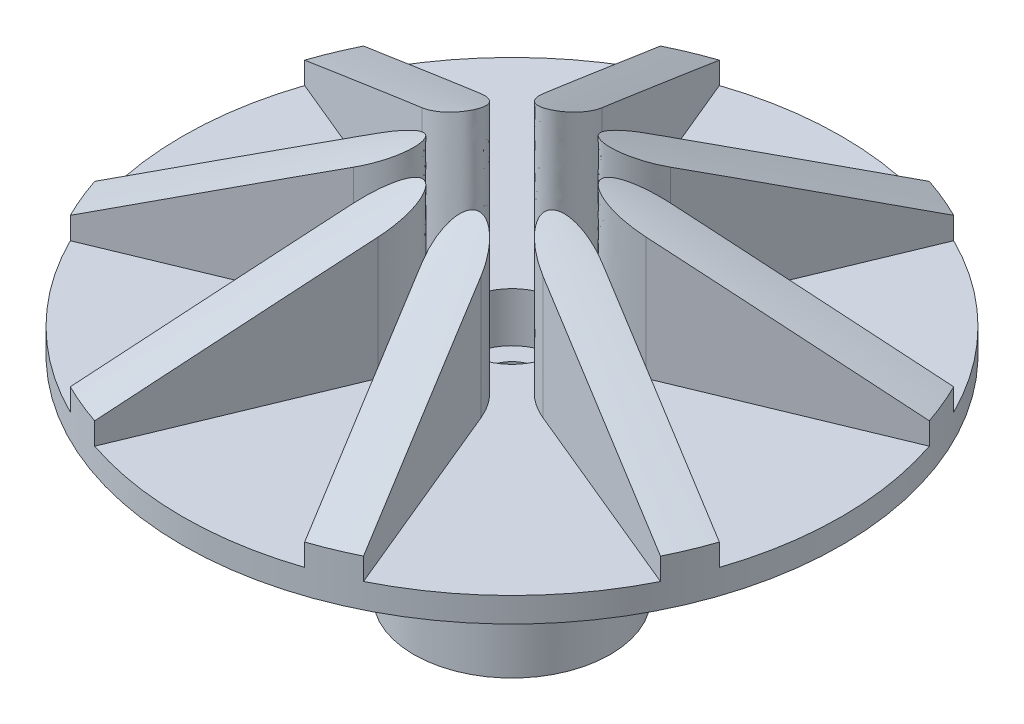
SolidWorks part; units mm, degrees
ref_plane "Front Plane" through (0, 0, 0) normal (0, 0, 1) x (1, 0, 0)
ref_plane "Top Plane" through (0, 0, 0) normal (0, 1, 0) x (1, 0, 0)
ref_plane "Right Plane" through (0, 0, 0) normal (1, 0, 0) x (0, 0, -1)
sketch "Sketch1" plane through (0, 0, 0) normal (0, 1, 0) x (1, 0, 0)
  circle A0 centre (0, 0) radius 26.6319
  dimension "D1" = 53.2638
extrude "impeller plate" add sketch "Sketch1" along normal blind 2
sketch "Sketch6" plane through (0, 0, 0) normal (0, -1, 0) x (-1, 0, 0)
  circle A0 centre (0, 0) radius 7.9375
  dimension "D1" = 15.875
extrude "boss" add sketch "Sketch6" along normal blind 17
sketch "Sketch7" plane through (0, -17, 0) normal (0, -1, 0) x (-1, 0, 0)
  circle A0 centre (0, 0) radius 2.1828
  dimension "D1" = 4.3656
extrude "bolt bore" cut sketch "Sketch7" against normal through all
sketch "Sketch8" plane through (0, -17, 0) normal (0, -1, 0) x (-1, 0, 0)
  circle A0 centre (0, 0) radius 4
  dimension "D1" = 8
extrude "shaft bore" cut sketch "Sketch8" against normal blind 12
sketch "Sketch9" plane through (0, 2, 0) normal (0, 1, 0) x (1, 0, 0)
  circle A0 centre (0, 0) radius 3.75
  dimension "D1" = 7.5
extrude "bolt head bore" cut sketch "Sketch9" against normal blind 4
sketch "Sketch11" plane through (0, -17, 0) normal (0, -1, 0) x (1, 0, 0)
  line L1 (-6, 1) -> (6, 1)
  line L2 (-6, 1) -> (-6, -1)
  line L3 (-6, -1) -> (6, -1)
  line L4 (6, 1) -> (6, -1)
  line L5 (-6, 1) -> (6, -1) construction
  line L6 (-6, -1) -> (6, 1) construction
  point P0 (0, 0)
  dimension "D1" = 12
  dimension "D2" = 2
extrude "dowel slot" cut sketch "Sketch11" against normal blind 3
sketch "Sketch12" plane through (0, 2, 0) normal (0, 1, 0) x (1, 0, 0)
  line L0 (0, 0) -> (26.6319, 0) construction
  line L1 (5.2568, 1.2794) -> (26.6012, 1.2794)
  line L2 (5.2568, -1.2794) -> (26.6012, -1.2794)
  circle A0 centre (0, 0) radius 26.6319 construction
  arc A3 (26.6012, -1.2794) -> (26.6012, 1.2794) centre (0, 0) ccw
  arc A4 (5.2568, -1.2794) -> (5.2568, 1.2794) centre (0, 0) ccw
  dimension "D3" = 10.8204
  dimension "D1" = 1.2794
  dimension "D2" = 1.2794
extrude "opening alingment cut" cut sketch "Sketch12" against normal blind 1
pattern_circular "opening alingment pattern" count 8 over 360 about axis through (0, 2, 0) along (0, 1, 0) of "opening alingment cut"
sketch "Sketch14" plane through (0, 2, 0) normal (0, 1, 0) x (1, 0, 0)
  line L0 (0, 0) -> (26.6319, 0) construction
  line L1 (26.6012, 1.2794) -> (5.2568, 1.2794) construction
  line L2 (7.6665, 5.1467) -> (9.0603, 1.7817) construction
  line L3 (25.244, 8.4852) -> (9.0603, 1.7817) construction
  line L4 (8.3634, 3.4642) -> (4.9984, 2.0704) construction
  line L5 (0, 0) -> (24.6047, 10.1916) construction
  line L7 (7.6665, 5.1467) -> (23.8502, 11.8502)
  line L9 (9.0603, 1.7817) -> (25.244, 8.4852)
  arc A2 (26.6012, -1.2794) -> (26.6012, 1.2794) centre (0, 0) ccw construction
  arc A5 (26.6012, 1.2794) -> (19.7145, 17.9052) centre (0, 0) ccw construction
  circle A6 centre (0, 0) radius 5.4102 construction
  circle A7 centre (0, 0) radius 5.4102 construction
  arc A8 (25.244, 8.4852) -> (23.8502, 11.8502) centre (0, 0) ccw
  ellipse E0 centre (8.3634, 3.4642) end of major axis (4.9984, 2.0704) minor radius 1.8211 (7.6665, 5.1467) -> (9.0603, 1.7817) ccw
  dimension "D1" = 22.5
extrude "one blade" add sketch "Sketch14" along normal blind 11.6738
sketch "Sketch15" plane through (0, 2, 0) normal (0, 1, 0) x (1, 0, 0)
  circle A0 centre (0, 0) radius 26.6319
  arc A1 (-19.7145, 17.9052) -> (-26.6012, 1.2794) centre (0, 0) ccw construction
  circle A2 centre (0, 0) radius 3.75
  circle A3 centre (0, 0) radius 3.75 construction
extrude "opening alignment fill" add sketch "Sketch15" against normal blind 2
pattern_circular "CirPattern2" count 8 over 360 about axis through (0, 2, 0) along (0, 1, 0) of "one blade"
sketch "Sketch16" plane through (0, 0, 0) normal (1, 0, 0) x (0, 0, -1)
  line L0 (0, 0) -> (0, 13.6738) construction
  line L2 (26.6319, 0) -> (26.6319, 3.778) construction
  line L3 (0, 13.6738) -> (5.4102, 13.6738) construction
  line L4 (5.4102, 13.6738) -> (26.6319, 3.778)
  line L5 (26.6319, 3.778) -> (26.6319, 13.6738)
  line L6 (26.6319, 13.6738) -> (5.4102, 13.6738)
  line L7 (-26.6319, 0) -> (26.6319, 0) construction
  dimension "D1" = 3.778
  dimension "D2" = 5.4102
  dimension "D3" = 26.6319
  dimension "D4" = 13.6738
revolve "angle cut" cut sketch "Sketch16" angle 360 about L0
equation "\"z\" = 8 \t\t\t'number of blades"
equation "\"de_length\" = 10mm\t\t'entrance eye consistent length"
equation "\"av\" = \"ae\"*\"av_ratio\"\t\t'area between just two blades"
equation "\"d2\" = 2.097in \t\t\t'outer diameter of the impeller"
equation "\"theta\" = 25\t\t\t'angle of blades from inner to outer "
equation "\"b2\" = .07in\t\t\t\t\t\t\t'tip height from disc surface at d2"
equation "\"b1\" = \"b2\" + (\"d2\"/2 - \"de\"/2)*tan(\"theta\") \t\t\t'tip height from disc surface at inlet eye"
equation "\"impeller base thickness\"= 2mm"
equation "\"impeller dowel diameter\" = 2mm"
equation "\"impeller bolt head diameter\" = \"m4 head bore diameter\""
equation "\"impeller bolt head depth\" = 4mm"
equation "\"impeller bolt stop depth\" = 3mm"
equation "\"impeller bolt bore\" = \"m4 clearance\""
equation "\"impeller shaft bore depth\" = 12mm"
equation "\"impeller shaft bore\" = 8mm"
equation "\"impeller boss depth\" = \"impeller shaft bore depth\"+\"impeller bolt stop depth\"+\"impeller bolt head depth\"-\"impeller base thickness\""
equation "\"impeller boss diameter\" = \"upper seal ID\""
equation "\"impeller dowel length\" = 2mm*2 + \"impeller shaft bore\""
equation "\"D1@Sketch1\"=\"d2\""
equation "\"D1@impeller plate\" = \"impeller base thickness\""
equation "\"D1@Sketch6\"=\"impeller boss diameter\""
equation "\"D1@boss\" = \"impeller boss depth\""
equation "\"D1@Sketch7\"=\"impeller bolt bore\""
equation "\"D1@Sketch8\"= \"impeller shaft bore\""
equation "\"D1@shaft bore\" = \"impeller shaft bore depth\""
equation "\"D1@Sketch9\"=\"impeller bolt head diameter\""
equation "\"D1@bolt head bore\" = \"impeller bolt head depth\""
equation "\"D1@Sketch11\"=\"impeller dowel length\""
equation "\"D2@Sketch11\"=\"impeller dowel diameter\""
equation "\"D1@dowel slot\" = \"impeller dowel diameter\" + 1mm"
equation "\"ae\" = 3.14*(\"de\"^2)/4\t\t'entrance eye area'"
equation "\"av_ratio\" = .325\t\t'ratio of av/ae at N_s of 470, range is .275 to .375, .325 ideal. High ratio means bigger area means smaller blades"
equation "\"s_open\" = \"av\"/\"b1\"\t\t'width of open area"
equation "\"de\" = 0.426in\t\t\t'entrance eye diameter"
equation "\"ce\" = 3.14*\"de\"\t\t'entrance eye circumference"
equation "\"D1@Sketch12\"=\"s_open\"/2"
equation "\"D3@Sketch12\"=\"de\""
equation "\"D1@opening alingment pattern\" = \"z\""
equation "\"D2@Sketch12\"=\"s_open\"/2"
equation "\"D1@one blade\" = \"b1\""
equation "\"D1@opening alignment fill\" = \"impeller base thickness\""
equation "\"D1@CirPattern2\"=\"z\""
equation "\"D1@Sketch16\"=\"impeller base thickness\"+\"b2\""
equation "\"D2@Sketch16\"=\"de\"/2"
equation "\"D3@Sketch16\"=\"d2\"/2"
equation "\"D1@Sketch14\"=360/\"z\"/2"
equation "\"D4@Sketch16\"=\"b1\"+\"impeller base thickness\""
equation "\"s\"=\"ce\" - \"z\"*\"s_open\""
equation "\"upper seal ID\"= 0.625in"
equation "\"m4 clearance\" = 0.171875in \t'this is 11/64 bit for 4.36mm"
equation "\"m4 tap\" = 0.125in\t\t'this is 1/8 bit for 3.17mm"
equation "\"m4 head bore diameter\" = 7.5mm"
equation "\"m4 head bore depth\" = 5mm\t'actual is ~4mm"
